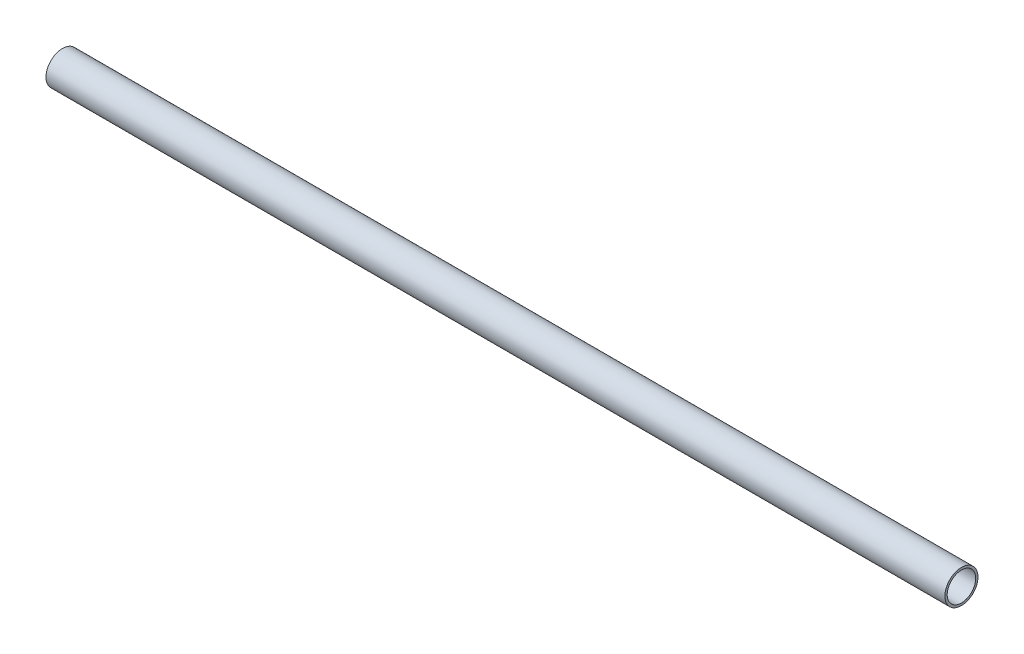
SolidWorks part; units mm, degrees
ref_plane "Front Plane" through (0, 0, 0) normal (0, 0, 1) x (1, 0, 0)
ref_plane "Top Plane" through (0, 0, 0) normal (0, 1, 0) x (1, 0, 0)
ref_plane "Right Plane" through (0, 0, 0) normal (1, 0, 0) x (0, 0, -1)
ref_axis "Axis1" through (-2, 0, 0) along (1, 0, 0)
sketch "Sketch1" plane through (0, 0, 0) normal (1, 0, 0) x (0, 0, -1)
  circle A0 centre (0, 0) radius 0.635
  circle A1 centre (0, 0) radius 0.7366
  dimension "D1" = 1.4732
  dimension "D2" = 1.27
extrude "Boss-Extrude1" add sketch "Sketch1" along normal blind 40
equation "\"Do\"=8.5mm"
equation "\"Lo\"=10"
equation "\"screw_diam\" = 3.5mm"
equation "\"wheel_Do\"=12.5mm"
equation "\"wheel_thickness\"=4mm"
equation "\"Collet_diameter\"=4.3"
equation "\"clearance\"= 0.5mm"
equation "\"handle_body_width\" = 10mm"
equation "\"finger_diameter\"=35"
equation "\"collet_lid_diameter\"=10"
equation "\"screw_cap_diam\"=5.15"
equation "\"handle_thickness\"=12.5mm"
equation "\"post_hole_diam\"=2"
equation "\"roll_rod_diam\"= 6.5 "
equation "\"roll_rod_length\"=6.6"
equation "\"disc_diam\"=5"
equation "\"disc_width\"=1.5"
equation "\"arm_width\"=5"
equation "\"arm_thickness\"=4.5"
equation "\"wheel_total_diam\"=30"
equation "\"spring_diam\"=4.1"
equation "\"collet_length\" = 18.75mm"
equation "\"tip_length\" = 40mm"
equation "\"D1@Boss-Extrude1\"=\"tip_length\""
